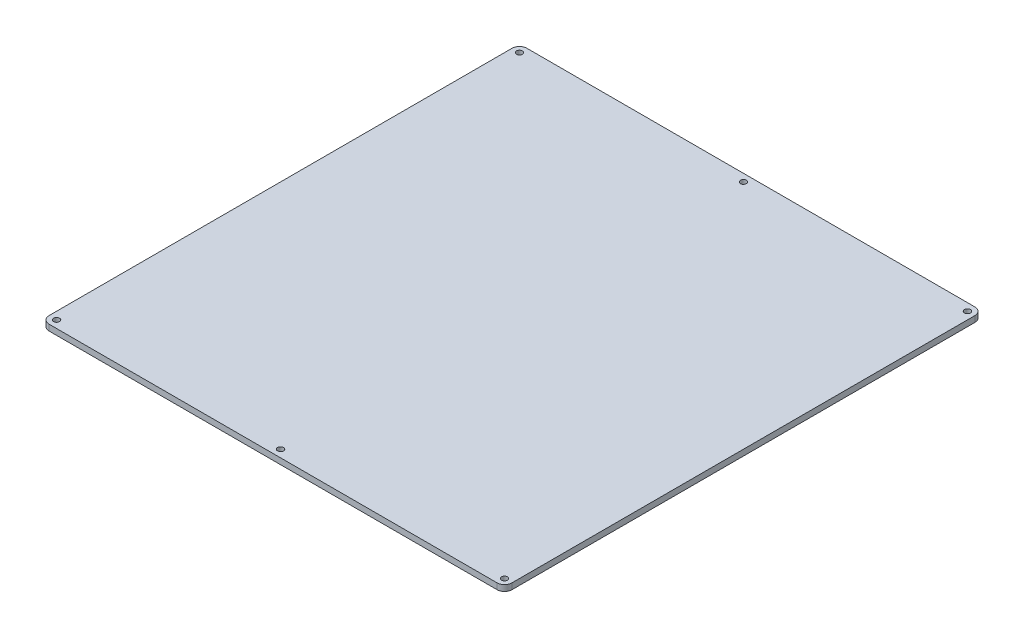
SolidWorks part; units mm, degrees
ref_plane "Front Plane" through (0, 0, 0) normal (0, 0, 1) x (1, 0, 0)
ref_plane "Top Plane" through (0, 0, 0) normal (0, 1, 0) x (1, 0, 0)
ref_plane "Right Plane" through (0, 0, 0) normal (1, 0, 0) x (0, 0, -1)
sketch "Sketch1" plane through (0, 0, 0) normal (0, 1, 0) x (1, 0, 0)
  line L0 (0, 0) -> (-150, 0) construction
  line L1 (0, 0) -> (150, 0) construction
  line L2 (0, 0) -> (0, 310) construction
  line L3 (0, 310) -> (-150, 310) construction
  line L4 (0, 310) -> (150, 310) construction
  line L5 (-155, 310) -> (-155, 0)
  line L6 (-150, -5) -> (150, -5)
  line L7 (155, 0) -> (155, 310)
  line L8 (150, 315) -> (-150, 315)
  circle A0 centre (-150, 310) radius 2
  circle A1 centre (0, 310) radius 2
  circle A2 centre (150, 310) radius 2
  circle A3 centre (-150, 0) radius 2
  circle A4 centre (0, 0) radius 2
  circle A5 centre (150, 0) radius 2
  arc A6 (-155, 0) -> (-150, -5) centre (-150, 0) ccw
  arc A7 (150, -5) -> (155, 0) centre (150, 0) ccw
  arc A8 (155, 310) -> (150, 315) centre (150, 310) ccw
  arc A9 (-150, 315) -> (-155, 310) centre (-150, 310) ccw
  dimension "D3" = 4
  dimension "D4" = 5
  dimension "D1" = 150
  dimension "D2" = 310
extrude "Boss-Extrude1" add sketch "Sketch1" along normal blind 4
